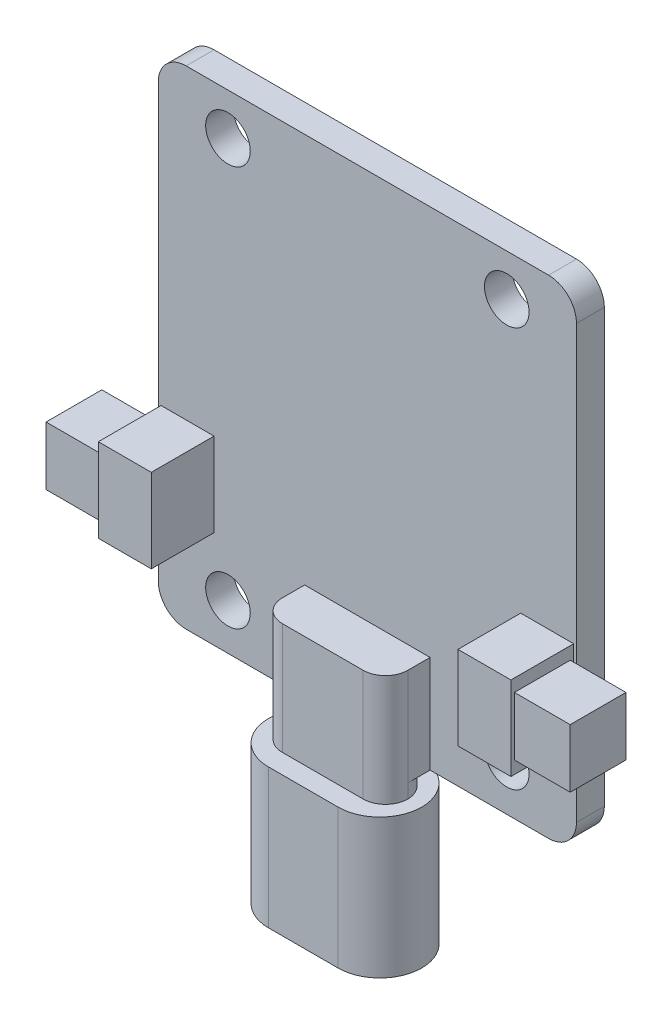
SolidWorks part; units mm, degrees
ref_plane "前视基准面" through (0, 0, 0) normal (0, 0, 1) x (1, 0, 0)
ref_plane "上视基准面" through (0, 0, 0) normal (0, 1, 0) x (1, 0, 0)
ref_plane "右视基准面" through (0, 0, 0) normal (1, 0, 0) x (0, 0, -1)
sketch "草图1" plane through (0, 0, 0) normal (0, 0, 1) x (1, 0, 0)
  line L1 (0, 0) -> (30, 0)
  line L2 (0, 0) -> (0, 35)
  line L3 (0, 35) -> (30, 35)
  line L4 (30, 0) -> (30, 35)
  line L5 (5, 32) -> (25, 32) construction
  line L6 (5, 32) -> (5, 3.3) construction
  line L7 (5, 3.3) -> (25, 3.3) construction
  line L8 (25, 32) -> (25, 3.3) construction
  circle A2 centre (5, 32) radius 1.6
  circle A3 centre (25, 32) radius 1.6
  circle A4 centre (5, 3.3) radius 1.6
  circle A5 centre (25, 3.3) radius 1.6
  dimension "D7" = 3.2
  dimension "D1" = 30
  dimension "D2" = 35
  dimension "D3" = 28.7
  dimension "D4" = 20
  dimension "D5" = 5
  dimension "D6" = 3
extrude "凸台-拉伸1" add sketch "草图1" along normal blind 2
sketch "草图2" plane through (0, 0, 2) normal (0, 0, 1) x (1, 0, 0)
  line L5 (0, 0) -> (30, 0) construction
  line L6 (10.5, 7) -> (19.5, 7)
  line L7 (10.5, 7) -> (10.5, -1)
  line L8 (10.5, -1) -> (19.5, -1)
  line L9 (19.5, 7) -> (19.5, -1)
  line L10 (15, 35) -> (15, -49965) construction
  line L11 (30, 35) -> (0, 35) construction
  point P10 (15, 35)
  point P11 (15, 0)
  point P12 (15, 7)
  dimension "D1" = 1
  dimension "D2" = 7
  dimension "D3" = 9
extrude "凸台-拉伸2" add sketch "草图2" along normal blind 3.2
sketch "草图3" plane through (0, 0, 2) normal (0, 0, 1) x (1, 0, 0)
  line L6 (15, 35) -> (15, -49965) construction
  line L7 (30, 35) -> (0, 35) construction
  line L8 (10.5, -1) -> (19.5, -1) construction
  line L19 (0, 0) -> (10.5, 0) construction
  line L20 (0.2, 13) -> (4, 13)
  line L21 (0.2, 13) -> (0.2, 7)
  line L22 (0.2, 7) -> (4, 7)
  line L23 (4, 13) -> (4, 7)
  line L24 (0, 35) -> (0, 0) construction
  line L25 (26, 13) -> (26, 7)
  line L26 (29.8, 7) -> (26, 7)
  line L27 (29.8, 13) -> (29.8, 7)
  line L28 (29.8, 13) -> (26, 13)
  point P12 (15, 35)
  point P15 (15, -1)
  dimension "D1" = 7
  dimension "D2" = 4
  dimension "D3" = 6
  dimension "D4" = 0.2
extrude "凸台-拉伸3" add sketch "草图3" along normal blind 4.5
sketch "草图4" plane through (0, 0, 0) normal (0, 0, -1) x (-1, 0, 0)
  line L0 (0, 0) -> (-30, 0) construction
  line L1 (-8, 0) -> (-22, 0)
  line L2 (-8, 0) -> (-8, 6)
  line L3 (-8, 6) -> (-22, 6)
  line L4 (-22, 0) -> (-22, 6)
  line L5 (-15, 35) -> (-15, -49965) construction
  line L7 (-30, 35) -> (0, 35) construction
  point P10 (-15, 35)
  point P11 (-15, 0)
  dimension "D1" = 14
  dimension "D2" = 6
extrude "凸台-拉伸4" add sketch "草图4" along normal blind 1.5
fillet "圆角1" radius 1.6 4 edges at (19.5, 3, 5.2) (19.5, -0.5, 2) (10.5, -0.5, 2) (10.5, 3, 5.2)
fillet "圆角2" radius 2 4 edges at (30, 35, 1) (0, 35, 1) (0, 0, 1) (30, 0, 1)
sketch "草图5" plane through (0.2, 0, 0) normal (-1, 0, 0) x (0, 0, 1)
  line L0 (2, 10) -> (50002, 10) construction
  line L1 (2.25, 7.9) -> (6.25, 7.9)
  line L2 (2.25, 7.9) -> (2.25, 12.1)
  line L3 (2.25, 12.1) -> (6.25, 12.1)
  line L4 (6.25, 7.9) -> (6.25, 12.1)
  line L5 (2, 13) -> (2, 7) construction
  line L6 (6.5, 13) -> (6.5, 7) construction
  line L7 (4.25, 13) -> (4.25, -49987) construction
  line L9 (6.5, 13) -> (2, 13) construction
  line L10 (6.5, 7) -> (2, 7) construction
  point P8 (2, 10)
  point P11 (6.5, 10)
  point P19 (4.25, 13)
  point P22 (4.25, 7)
  point P23 (2.25, 10)
  point P24 (4.25, 12.1)
  dimension "D1" = 4.2
  dimension "D2" = 4
extrude "凸台-拉伸5" add sketch "草图5" along normal blind 4
ref_plane "基准面1" through (15, 0, 0) normal (-1, 0, 0) x (0, 0, 1)
mirror "镜向1" about plane through (15, 0, 0) normal (-1, 0, 0) of "凸台-拉伸5"
sketch "草图6" plane through (0, -1, 0) normal (0, -1, 0) x (1, 0, 0)
  line L0 (17.5, 3.6) -> (12.5, 3.6) construction
  line L1 (17.5, 0.6) -> (12.5, 0.6)
  line L2 (17.5, 6.6) -> (12.5, 6.6)
  line L3 (12.1, 5.2) -> (17.9, 5.2) construction
  arc A0 (17.5, 0.6) -> (17.5, 6.6) centre (17.5, 3.6) ccw
  arc A1 (12.5, 6.6) -> (12.5, 0.6) centre (12.5, 3.6) ccw
  point P2 (15, 3.6)
  point P9 (15, 5.2)
  dimension "D3" = 3
  dimension "D1" = 1.6
  dimension "D2" = 5
extrude "凸台-拉伸6" add sketch "草图6" along normal blind 10
